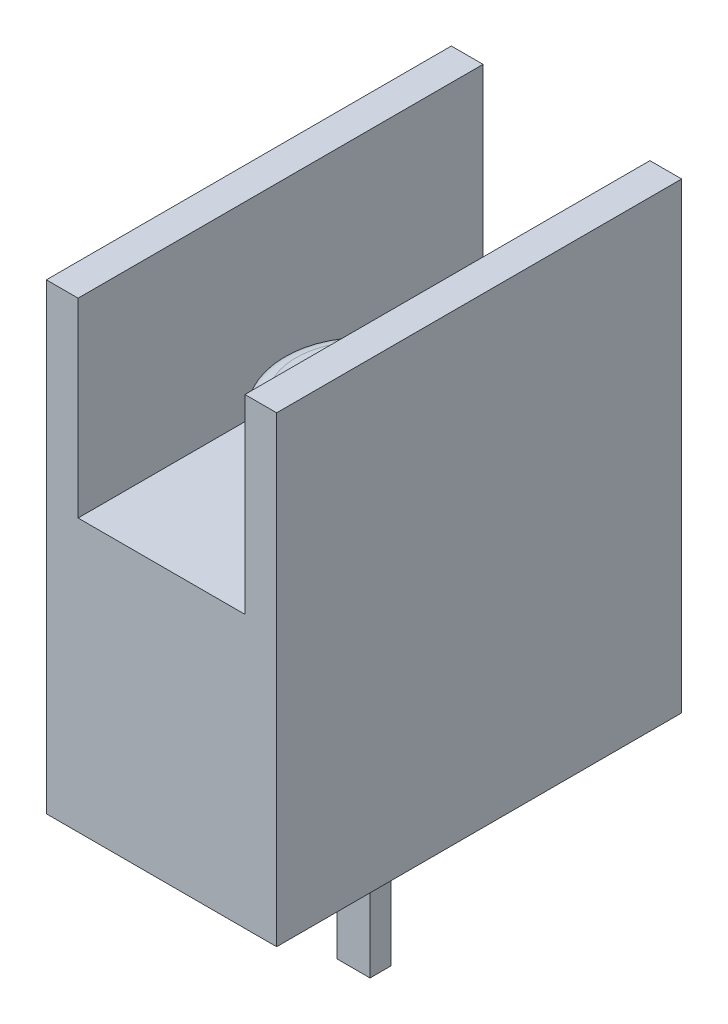
SolidWorks part; units mm, degrees
ref_plane "前视基准面" through (0, 0, 0) normal (0, 0, 1) x (1, 0, 0)
ref_plane "上视基准面" through (0, 0, 0) normal (0, 1, 0) x (1, 0, 0)
ref_plane "右视基准面" through (0, 0, 0) normal (1, 0, 0) x (0, 0, -1)
sketch "草图1" plane through (0, 0, 0) normal (0, 1, 0) x (1, 0, 0)
  line L0 (-11.1447, 0) -> (12.1543, 0) construction
  line L1 (-3.81, 6.7) -> (3.81, 6.7)
  line L2 (-3.81, 6.7) -> (-3.81, -6.7)
  line L3 (-3.81, -6.7) -> (3.81, -6.7)
  line L4 (3.81, 6.7) -> (3.81, -6.7)
  line L5 (0, 11.4931) -> (0, -8.9219) construction
  dimension "D1" = 7.62
  dimension "D2" = 13.4
extrude "拉伸1" add sketch "草图1" along normal blind 15.3
sketch "草图2" plane through (0, 15.3, 0) normal (0, 1, 0) x (-1, 0, 0)
  line L0 (3.81, 6.7) -> (-3.81, 6.7) construction
  line L1 (-2.76, 6.7) -> (2.76, 6.7)
  line L3 (-2.76, 6.7) -> (-2.76, -6.7)
  line L4 (-2.76, -6.7) -> (2.76, -6.7)
  line L5 (2.76, 6.7) -> (2.76, -6.7)
  line L6 (-3.81, -6.7) -> (3.81, -6.7) construction
  line L7 (-3.81, 6.7) -> (-3.81, -6.7) construction
  line L10 (3.81, -6.7) -> (3.81, 6.7) construction
  dimension "D1" = 1.05
  dimension "D2" = 1.05
extrude "切除-拉伸1" cut sketch "草图2" against normal offset from surface (6.3 mm away) 9 up to face at (0, 0, 0)
sketch "草图3" plane through (0, 0, 0) normal (0, -1, 0) x (1, 0, 0)
  line L0 (-1.1261, 0) -> (1.1036, 0) construction
  line L1 (-0.55, 0.35) -> (0.55, 0.35)
  line L2 (-0.55, 0.35) -> (-0.55, -0.35)
  line L3 (-0.55, -0.35) -> (0.55, -0.35)
  line L4 (0.55, 0.35) -> (0.55, -0.35)
  line L5 (0, 0.8666) -> (0, -0.8367) construction
  dimension "D2" = 0.7
  dimension "D1" = 1.1
extrude "拉伸2" add sketch "草图3" along normal blind 5.7
sketch "草图4" plane through (0, 9, 0) normal (0, 1, 0) x (-1, 0, 0)
  line L0 (-9.5136, 0) -> (8.6579, 0) construction
  line L1 (0, -7.7686) -> (0, 8.3952) construction
  circle A1 centre (0, 0) radius 2.75
  dimension "D1" = 5.5
extrude "凸台-拉伸1" add sketch "草图4" along normal blind 1.5
fillet "圆角1" radius 0.5 1 edges at (0, 10.5, -2.75)
